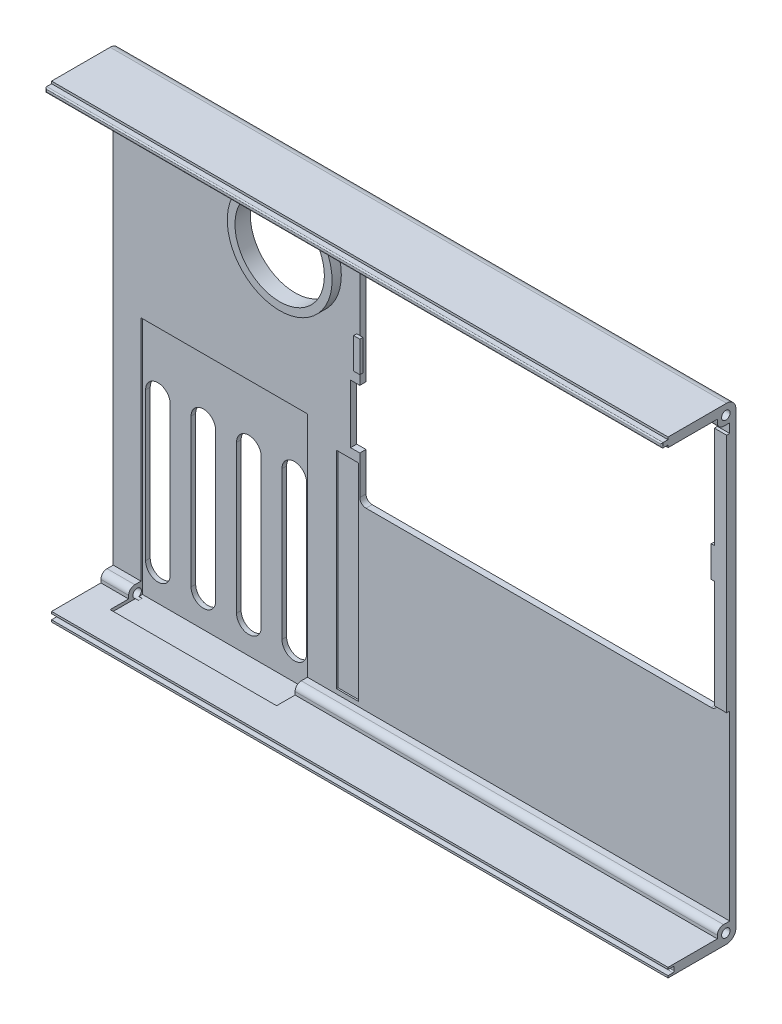
SolidWorks part; units mm, degrees
ref_plane "Front Plane" through (0, 0, 0) normal (0, 0, 1) x (1, 0, 0)
ref_plane "Top Plane" through (0, 0, 0) normal (0, 1, 0) x (1, 0, 0)
ref_plane "Right Plane" through (0, 0, 0) normal (1, 0, 0) x (0, 0, -1)
sketch "Sketch1" plane through (0, 0, 0) normal (0, 0, 1) x (1, 0, 0)
  line L1 (105, -90.3987) -> (-95, -90.3987)
  line L2 (105, -90.3987) -> (105, 61.6013)
  line L3 (105, 61.6013) -> (-95, 61.6013)
  line L4 (-95, -90.3987) -> (-95, 61.6013)
  line L5 (105, -90.3987) -> (-95, 61.6013) construction
  line L6 (105, 61.6013) -> (-95, -90.3987) construction
  point P0 (5, -14.3987)
  dimension "D1" = 200
  dimension "D2" = 152
extrude "body" add sketch "Sketch1" along normal blind 2
sketch "Sketch3" plane through (0, 0, 0) normal (0, 0, -1) x (-1, 0, 0)
  line L0 (95, -54.3987) -> (-105, -54.3987) construction
  line L1 (95, 61.6013) -> (95, -90.3987) construction
  line L2 (-105, -90.3987) -> (-105, 61.6013) construction
  line L3 (66.25, -78.3987) -> (66.25, -30.3987) construction
  line L4 (62.25, -78.3987) -> (62.25, -30.3987)
  line L5 (70.25, -78.3987) -> (70.25, -30.3987)
  line L6 (95, -30.3987) -> (-105, -30.3987) construction
  line L7 (81, -78.3987) -> (81, -30.3987) construction
  line L8 (95, -78.3987) -> (-105, -78.3987) construction
  line L9 (77, -78.3987) -> (77, -30.3987)
  line L10 (85, -78.3987) -> (85, -30.3987)
  line L11 (51.5, -78.3987) -> (51.5, -30.3987) construction
  line L12 (47.5, -78.3987) -> (47.5, -30.3987)
  line L13 (55.5, -78.3987) -> (55.5, -30.3987)
  line L14 (36.75, -78.3987) -> (36.75, -30.3987) construction
  line L15 (32.75, -78.3987) -> (32.75, -30.3987)
  line L16 (40.75, -78.3987) -> (40.75, -30.3987)
  line L17 (95, -90.3987) -> (95, 61.6013) construction
  line L18 (-105, 61.6013) -> (95, 61.6013) construction
  line L19 (95, -90.3987) -> (-105, -90.3987) construction
  line L20 (-105, -90.3987) -> (-105, 61.6013) construction
  circle A0 centre (38, 34.1013) radius 14.5
  arc A1 (62.25, -78.3987) -> (70.25, -78.3987) centre (66.25, -78.3987) ccw
  arc A2 (70.25, -30.3987) -> (62.25, -30.3987) centre (66.25, -30.3987) ccw
  arc A3 (77, -78.3987) -> (85, -78.3987) centre (81, -78.3987) ccw
  arc A4 (85, -30.3987) -> (77, -30.3987) centre (81, -30.3987) ccw
  arc A5 (47.5, -78.3987) -> (55.5, -78.3987) centre (51.5, -78.3987) ccw
  arc A6 (55.5, -30.3987) -> (47.5, -30.3987) centre (51.5, -30.3987) ccw
  arc A7 (32.75, -78.3987) -> (40.75, -78.3987) centre (36.75, -78.3987) ccw
  arc A8 (40.75, -30.3987) -> (32.75, -30.3987) centre (36.75, -30.3987) ccw
  point P10 (66.25, -54.3987)
  point P21 (81, -54.3987)
  point P27 (51.5, -54.3987)
  point P34 (36.75, -54.3987)
  dimension "D1" = 29
  dimension "D2" = 27.5
  dimension "D3" = 57
  dimension "D4" = 10
  dimension "D5" = 12
  dimension "D6" = 24
  dimension "D7" = 6.75
  dimension "D8" = 8
  dimension "D9" = 8
  dimension "D10" = 8
  dimension "D11" = 8
  dimension "D12" = 6.75
  dimension "D13" = 52.25
  dimension "D14" = 6.75
extrude "fan_exhaust_grill" cut sketch "Sketch3" against normal through all
sketch "Sketch12" plane through (0, 0, 2) normal (0, 0, 1) x (1, 0, 0)
  line L0 (-95, -90.3987) -> (-95, 61.6013) construction
  line L1 (105, -90.3987) -> (-95, -90.3987)
  line L2 (105, -90.3987) -> (105, -84.3987)
  line L3 (105, -84.3987) -> (-95, -84.3987)
  line L4 (-95, -90.3987) -> (-95, -84.3987)
  line L6 (105, 61.6013) -> (-95, 61.6013)
  line L7 (105, 61.6013) -> (105, 55.6013)
  line L8 (105, 55.6013) -> (-95, 55.6013)
  line L9 (-95, 61.6013) -> (-95, 55.6013)
  dimension "D1" = 6
  dimension "D2" = 6
extrude "side_walls" add sketch "Sketch12" along normal blind 20
sketch "Sketch14" plane through (105, 0, 0) normal (1, 0, 0) x (0, 0, -1)
  line L0 (-22, -90.3987) -> (0, -90.3987) construction
  line L1 (0, -90.3987) -> (0, 61.6013) construction
  line L2 (-22, 61.6013) -> (0, 61.6013) construction
  circle A0 centre (-3.25, -87.1487) radius 1.375
  circle A1 centre (-3.25, 58.3513) radius 1.375
  dimension "D1" = 2.75
  dimension "D2" = 2.75
  dimension "D3" = 3.25
  dimension "D4" = 3.25
  dimension "D5" = 3.25
  dimension "D6" = 3.25
  dimension "D7" = 145.5
extrude "mount_holes_l" cut sketch "Sketch14" against normal blind 10 and the other way through all
sketch "Sketch16" plane through (-95, 0, 0) normal (-1, 0, 0) x (0, 0, 1)
  line L0 (0, -90.3987) -> (0, 61.6013) construction
  line L2 (22, 61.6013) -> (0, 61.6013) construction
  line L3 (22, -90.3987) -> (0, -90.3987) construction
  circle A0 centre (3.25, -87.1487) radius 1.375
  circle A1 centre (3.25, 58.3513) radius 1.375
  dimension "D1" = 2.75
  dimension "D4" = 2.75
  dimension "D2" = 3.25
  dimension "D3" = 3.25
  dimension "D5" = 3.25
  dimension "D6" = 3.25
extrude "mount_holes_r" cut sketch "Sketch16" against normal blind 10
sketch "Sketch18" plane through (105, 0, 0) normal (1, 0, 0) x (0, 0, -1)
  line L1 (-22, -84.3987) -> (-6, -84.3987)
  line L2 (-22, -84.3987) -> (-22, -87.3987)
  line L3 (-22, -87.3987) -> (-6, -87.3987)
  line L4 (-6, -84.3987) -> (-6, -87.3987)
  line L5 (-22, 55.6013) -> (-6, 55.6013)
  line L6 (-22, 55.6013) -> (-22, 58.6013)
  line L7 (-22, 58.6013) -> (-6, 58.6013)
  line L8 (-6, 55.6013) -> (-6, 58.6013)
  dimension "D1" = 3
  dimension "D2" = 16
  dimension "D3" = 3
  dimension "D4" = 16
extrude "wall_reduce" cut sketch "Sketch18" against normal through all
sketch "Sketch19" plane through (0, 0, 22) normal (0, 0, 1) x (1, 0, 0)
  line L0 (-95, -90.3987) -> (-95, 61.6013) construction
  line L1 (-95, -89.7487) -> (105, -89.7487)
  line L2 (-95, -89.7487) -> (-95, -88.0487)
  line L3 (-95, -88.0487) -> (105, -88.0487)
  line L4 (105, -89.7487) -> (105, -88.0487)
  line L5 (105, -90.3987) -> (105, 61.6013) construction
  line L6 (-95, -90.3987) -> (105, -90.3987) construction
  line L7 (-95, -87.3987) -> (105, -87.3987) construction
  dimension "D1" = 0.65
  dimension "D2" = 1.7
  dimension "D3" = 0.65
extrude "groove" cut sketch "Sketch19" against normal blind 2
sketch "Sketch20" plane through (0, 0, 22) normal (0, 0, 1) x (1, 0, 0)
  line L0 (-95, -90.3987) -> (-95, 61.6013) construction
  line L1 (-95, 59.3513) -> (105, 59.3513)
  line L2 (-95, 59.3513) -> (-95, 60.8513)
  line L3 (-95, 60.8513) -> (105, 60.8513)
  line L4 (105, 59.3513) -> (105, 60.8513)
  line L5 (105, -90.3987) -> (105, 61.6013) construction
  line L6 (105, 61.6013) -> (-95, 61.6013) construction
  dimension "D1" = 0.75
  dimension "D2" = 1.5
extrude "notch" add sketch "Sketch20" along normal blind 2
sketch "Sketch21" plane through (0, 0, 2) normal (0, 0, 1) x (1, 0, 0)
  line L0 (105, -90.3987) -> (105, 61.6013) construction
  line L1 (101, -27.3987) -> (-15, -27.3987)
  line L2 (101, -27.3987) -> (101, 55.1013)
  line L3 (101, 55.1013) -> (-15, 55.1013)
  line L4 (-15, -27.3987) -> (-15, 55.1013)
  line L5 (105, 61.6013) -> (-95, 61.6013) construction
  dimension "D1" = 116
  dimension "D2" = 82.5
  dimension "D3" = 4
  dimension "D4" = 6.5
extrude "batt_cut" cut sketch "Sketch21" against normal through all
fillet "Fillet1" radius 3 2 edges at (5, -90.3987, 0) (5, 61.6013, 0)
fillet "Fillet2" radius 2 2 edges at (5, -84.3987, 6) (5, 55.6013, 6)
fillet "Fillet3" radius 0.4 6 edges at (5, 60.8513, 24) (105, 60.1013, 24) (5, 59.3513, 24) (-95, 60.1013, 24) (5, -89.7487, 20) (5, -88.0487, 20)
fillet "Fillet4" radius 2 4 edges at (-15, -27.3987, 1) (101, -27.3987, 1) (101, 55.1013, 1) (-15, 55.1013, 1)
sketch "Sketch22" plane through (0, 0, 2) normal (0, 0, 1) x (1, 0, 0)
  circle A0 centre (-38, 34.1013) radius 14.5
  circle A1 centre (-38, 34.1013) radius 17
  dimension "D1" = 29
  dimension "D2" = 34
extrude "fan_hole_supp" add sketch "Sketch22" along normal blind 3
sketch "Sketch23" plane through (0, 0, 2) normal (0, 0, 1) x (1, 0, 0)
  line L0 (105, -90.3987) -> (105, 61.6013) construction
  line L1 (105, 52.6013) -> (101, 52.6013)
  line L2 (105, 52.6013) -> (105, -25.3987)
  line L3 (105, -25.3987) -> (101, -25.3987)
  line L4 (101, 52.6013) -> (101, -25.3987)
  arc A0 (99, -27.3987) -> (101, -25.3987) centre (99, -25.3987) ccw construction
  dimension "D1" = 78
  dimension "D2" = 4
extrude "batt_cut_supp" add sketch "Sketch23" along normal blind 1
sketch "Sketch24" plane through (0, 0, 2) normal (0, 0, 1) x (1, 0, 0)
  line L0 (-95, -90.3987) -> (-95, 61.6013) construction
  line L1 (-86, -10.3987) -> (-32, -10.3987)
  line L2 (-86, -10.3987) -> (-86, -88.3987)
  line L3 (-86, -88.3987) -> (-32, -88.3987)
  line L4 (-32, -10.3987) -> (-32, -88.3987)
  line L5 (-95, -90.3987) -> (105, -90.3987) construction
  line L7 (-22.5, -15.8987) -> (-15.5, -15.8987)
  line L8 (-22.5, -15.8987) -> (-22.5, -82.8987)
  line L9 (-22.5, -82.8987) -> (-15.5, -82.8987)
  line L10 (-15.5, -15.8987) -> (-15.5, -82.8987)
  dimension "D1" = 9
  dimension "D2" = 2
  dimension "D3" = 54
  dimension "D4" = 78
  dimension "D5" = 9.5
  dimension "D6" = 7
  dimension "D7" = 67
  dimension "D8" = 5.5
  dimension "D9" = 5.5
extrude "Cut-Extrude1" cut sketch "Sketch24" against normal blind 10.5 from offset 10
sketch "Sketch25" plane through (0, 0, 2) normal (0, 0, 1) x (1, 0, 0)
  line L7 (-15, 53.1013) -> (-15, -25.3987) construction
  line L8 (-15, 6.1013) -> (-18, 6.1013)
  line L9 (-15, 6.1013) -> (-15, -12.8987)
  line L10 (-15, -12.8987) -> (-18, -12.8987)
  line L11 (-18, 6.1013) -> (-18, -12.8987)
  line L12 (-13, -27.3987) -> (99, -27.3987) construction
  dimension "D1" = 14.5
  dimension "D2" = 19
  dimension "D3" = 3
extrude "Cut-Extrude2" cut sketch "Sketch25" against normal through all
sketch "Sketch26" plane through (0, 0, 2) normal (0, 0, 1) x (1, 0, 0)
  line L0 (-15, 53.1013) -> (-15, 6.1013) construction
  line L1 (-15, 20.1013) -> (-16, 20.1013)
  line L2 (-15, 20.1013) -> (-15, 10.1013)
  line L3 (-15, 10.1013) -> (-16, 10.1013)
  line L4 (-16, 20.1013) -> (-16, 10.1013)
  line L10 (99, 55.1013) -> (-13, 55.1013) construction
  dimension "D4" = 1
  dimension "D5" = 10
  dimension "D6" = 35
extrude "Boss-Extrude1" add sketch "Sketch26" along normal blind 1
sketch "Sketch27" plane through (-15, 0, 0) normal (1, 0, 0) x (0, 0, -1)
  line L0 (-3, 10.1013) -> (-3, 20.1013) construction
  line L1 (-3, 20.1013) -> (-2, 20.1013)
  line L2 (-3, 20.1013) -> (-3, 10.1013)
  line L3 (-3, 10.1013) -> (-2, 10.1013)
  line L4 (-2, 20.1013) -> (-2, 10.1013)
  line L5 (-3, 20.1013) -> (-2, 20.1013) construction
extrude "Boss-Extrude2" add sketch "Sketch27" along normal blind 1
sketch "Sketch28" plane through (101, 0, 0) normal (-1, 0, 0) x (0, 0, 1)
  line L0 (0, -25.3987) -> (0, 53.1013) construction
  line L1 (2, 9.6013) -> (3, 9.6013)
  line L2 (2, 9.6013) -> (2, 19.6013)
  line L3 (2, 19.6013) -> (3, 19.6013)
  line L4 (3, 9.6013) -> (3, 19.6013)
  line L5 (3, 52.6013) -> (2, 52.6013) construction
  dimension "D1" = 1
  dimension "D2" = 2
  dimension "D3" = 10
  dimension "D4" = 33
extrude "Boss-Extrude3" add sketch "Sketch28" along normal blind 1
